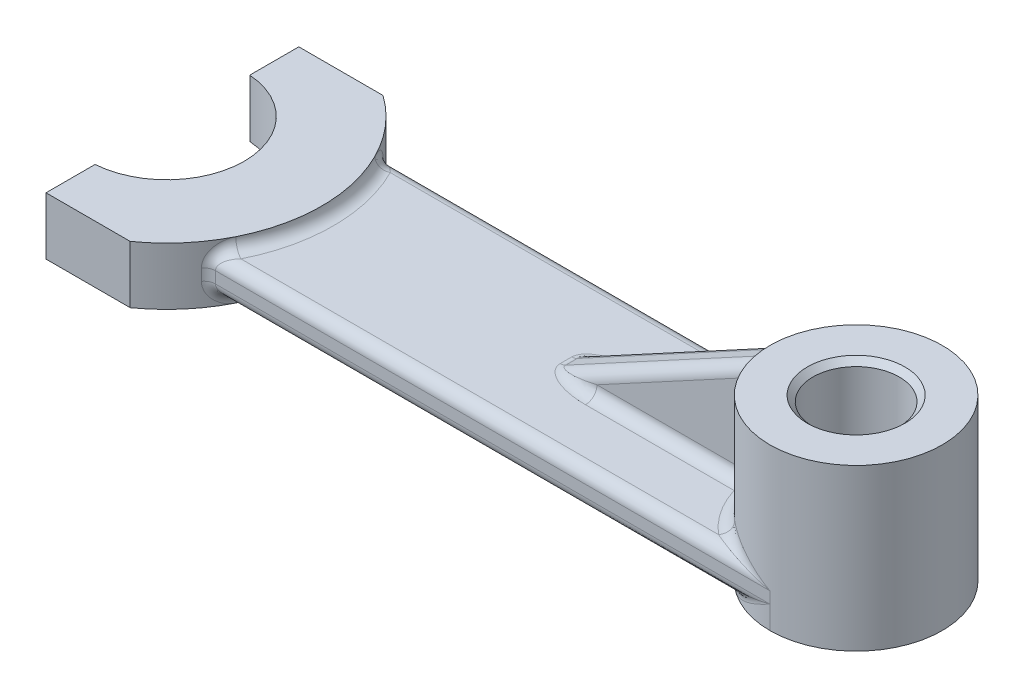
SolidWorks part; units mm, degrees
ref_plane "前视基准面" through (0, 0, 0) normal (0, 0, 1) x (1, 0, 0)
ref_plane "上视基准面" through (0, 0, 0) normal (0, 1, 0) x (1, 0, 0)
ref_plane "右视基准面" through (0, 0, 0) normal (1, 0, 0) x (0, 0, -1)
sketch "草图2" plane through (0, 0, 0) normal (0, 1, 0) x (1, 0, 0)
  circle A0 centre (0, 0) radius 27
  dimension "D1" = 54
extrude "凸台-拉伸1" add sketch "草图2" along normal blind 10
sketch "草图3" plane through (0, 10, 0) normal (0, 1, 0) x (1, 0, 0)
  line L0 (1, 26.9815) -> (1, -26.9815)
  circle A0 centre (0, 0) radius 27 construction
  dimension "D1" = 1
extrude "切除-拉伸1" cut sketch "草图3" against normal blind 10 and the other way through all flip side to cut
sketch "草图4" plane through (0, 10, 0) normal (0, 1, 0) x (1, 0, 0)
  line L0 (1, 22) -> (15.6525, 22)
  line L1 (1, 26.9815) -> (1, -26.9815) construction
  line L2 (0, 0) -> (9.8945, 0) construction
  arc A0 (1, -26.9815) -> (1, 26.9815) centre (0, 0) ccw construction
  dimension "D1" = 22
extrude "切除-拉伸2" cut sketch "草图4" against normal through all and the other way through all
mirror "镜向1" about plane through (0, 0, 0) normal (0, 0, 1) of "切除-拉伸2"
sketch "草图5" plane through (0, 10, 0) normal (0, 1, 0) x (1, 0, 0)
  circle A0 centre (0, 0) radius 13.5
  dimension "D1" = 27
extrude "切除-拉伸3" cut sketch "草图5" against normal through all
sketch "草图6" plane through (0, 0, 0) normal (0, 1, 0) x (1, 0, 0)
  line L1 (22.4499, -15) -> (120, -15)
  line L2 (22.4499, -15) -> (22.4499, 15)
  line L3 (22.4499, 15) -> (120, 15)
  arc A0 (15.6525, -22) -> (15.6525, 22) centre (0, 0) ccw construction
  arc A1 (120, -15) -> (120, 15) centre (120, 0) ccw
  point P8 (122.8295, -14.8654)
  dimension "D1" = 15
  dimension "D2" = 120
extrude "凸台-拉伸2" add sketch "草图6" along normal blind 6 from offset 2
sketch "草图7" plane through (0, 8, 0) normal (0, 1, 0) x (1, 0, 0)
  circle A0 centre (120, 0) radius 15
  arc A1 (120, -15) -> (120, 15) centre (120, 0) ccw construction
extrude "凸台-拉伸3" add sketch "草图7" along normal blind 28 from surface starting at plane "上视基准面"
sketch "草图8" plane through (0, 28, 0) normal (0, 1, 0) x (1, 0, 0)
  circle A0 centre (120, 0) radius 7.5
  circle A1 centre (120, 0) radius 15 construction
  dimension "D1" = 15
extrude "切除-拉伸4" cut sketch "草图8" against normal through all
sketch "草图9" plane through (0, 0, 0) normal (0, 0, 1) x (1, 0, 0)
  line L0 (120, 28) -> (120, 0) construction
  line L1 (135, 28) -> (105, 28) construction
  line L2 (105, 0) -> (135, 0) construction
  point P0 (120, 14)
  point P7 (120, 16.2202)
  dimension "D1" = 14
hole_wizard "Ø8.0mm 暗销孔1" positions "草图9" profile "草图10" hole size "Ø8.0" standard "GB" end condition up to next
sketch "草图10" plane through (120, 14, 0) normal (1, 0, 0) x (0, -1, 0)
  line L0 (0, 0) -> (0, 15)
  line L1 (0, 15) -> (5.5, 15)
  line L2 (4, 13.5) -> (4, 0)
  line L5 (4, 0) -> (0, 0)
  line L7 (5.5, 15) -> (4, 13.5)
  line L8 (-5.5, 15) -> (-4, 13.5) construction
  line L11 (0, -6.35) -> (0, 107.95) construction
  dimension "通孔孔直径" = 8
  dimension "通孔孔深度" = 15
  dimension "远端锥形沉头孔直径" = 11
  dimension "远端锥形沉头孔角度" = 90
chamfer "倒角1" distance 1 angle 45 2 edges at (120, 0, 7.5) (120, 28, 7.5)
sketch "草图11" plane through (0, 0, 0) normal (0, 0, 1) x (1, 0, 0)
  line L0 (105, 26.9394) -> (70, 8)
  line L1 (22.4499, 8) -> (120, 8) construction
  line L2 (120, 8) -> (120, 2) construction
  line L3 (105, 28) -> (105, 8) construction
  point P7 (105, 26.9394)
  dimension "D1" = 50
rib "筋2" sketch "草图11" sketch "草图11" thickness 6 extrusion direction parallel to sketch draft on no parameters "D1"=6
fillet "圆角6" radius 2 10 edges at (27, 8, 0) (27, 2, 0) (22.4499, 5, 15) (71.225, 8, 15) (71.225, 2, 15) (71.225, 8, -15) (22.4499, 5, -15) (71.225, 2, -15) (87.6515, 17.5517, -3) (87.6515, 17.5517, 3)
fillet "圆角7" radius 2 12 edges at (115.2084, 2.4107, 14.2141) (115.2084, 2.4107, -14.2141) (115.2084, 7.5893, -14.2141) (115.2084, 7.5893, 14.2141) (105, 2, 0) (107.8348, 8, -8.7755) (89.7527, 8, -3) (71.2309, 8, -2.4142) (70, 8, 0) (71.2309, 8, 2.4142) (89.7527, 8, 3) (107.8348, 8, 8.7755)
